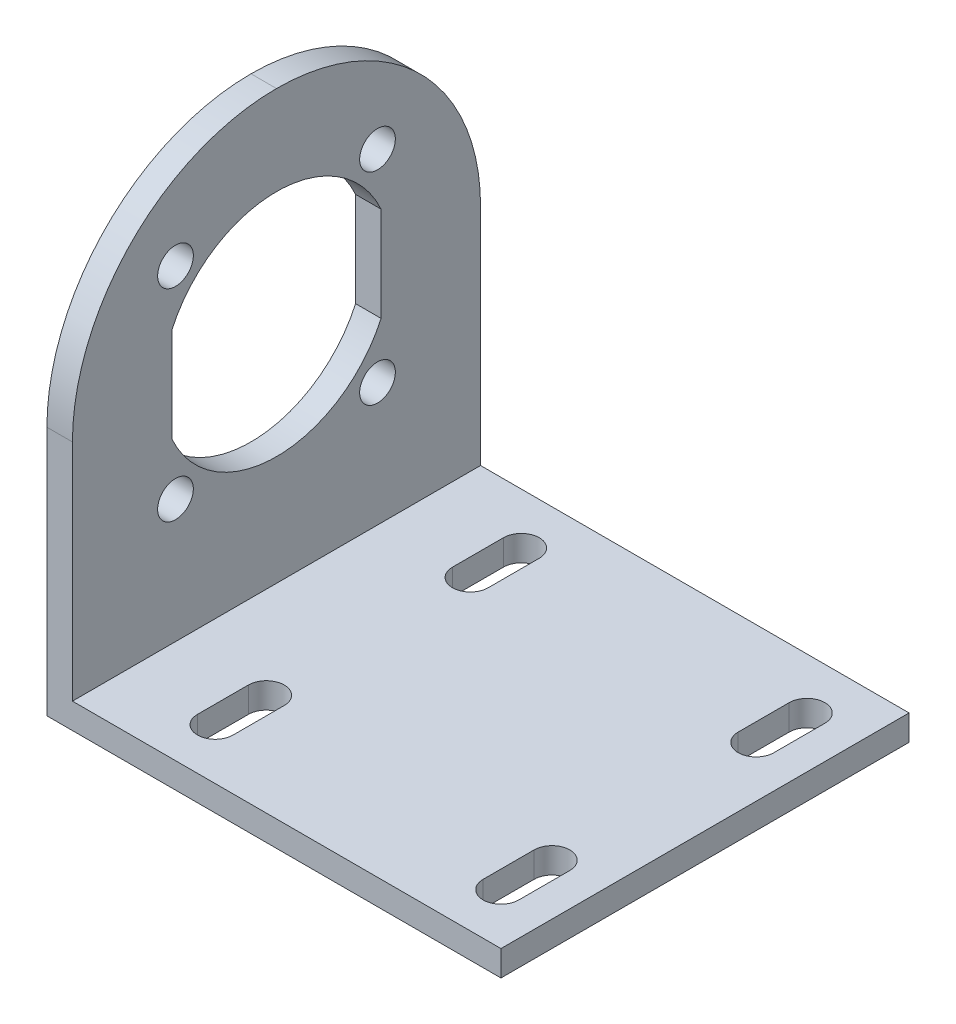
SolidWorks part; units mm, degrees
material "Plain Carbon Steel"
ref_plane "Front Plane"
ref_plane "Top Plane" through (0, 0, 0) normal (0, 1, 0) x (1, 0, 0)
ref_plane "Right Plane" through (0, 0, 0) normal (1, 0, 0) x (0, 0, -1)
sketch "Sketch1" plane through (0, 0, 0) normal (0, 0, 1) x (1, 0, 0)
  line L0 (0, 44.5) -> (0, 0)
  line L1 (0, 0) -> (44.5, 0)
  line L2 (44.5, 0) -> (44.5, 2.5)
  line L3 (44.5, 2.5) -> (2.5, 2.5)
  line L4 (2.5, 2.5) -> (2.5, 44.5)
  line L5 (2.5, 44.5) -> (0, 44.5)
  dimension "D1" = 44.5
  dimension "D2" = 44.5
  dimension "D3" = 2.5
extrude "Boss-Extrude1" add sketch "Sketch1" along normal mid plane 40
fillet "Fillet1" radius 20 2 edges at (1.25, 44.5, -20) (1.25, 44.5, 20)
sketch "Sketch2" plane through (2.5, 0, 0) normal (1, 0, 0) x (0, 0, -1)
  line L0 (10.25, 29.1368) -> (10.25, 19.8632)
  line L1 (-10.25, 29.1368) -> (-10.25, 19.8632)
  line L2 (0, 24.5) -> (9.8995, 14.6005) construction
  line L3 (0, 24.5) -> (4.182, 24.5) construction
  arc A0 (10.25, 29.1368) -> (-10.25, 29.1368) centre (0, 24.5) ccw
  arc A1 (-10.25, 19.8632) -> (10.25, 19.8632) centre (0, 24.5) ccw
  circle A2 centre (0, 24.5) radius 14 construction
  circle A3 centre (9.8995, 14.6005) radius 1.75
  circle A4 centre (-9.8995, 14.6005) radius 1.75
  circle A5 centre (-9.8995, 34.3995) radius 1.75
  circle A6 centre (9.8995, 34.3995) radius 1.75
  point P20 (0, 24.5)
  dimension "D1" = 22.5
  dimension "D4" = 3.5
  dimension "D5" = 28
  dimension "D2" = 10.25
  dimension "D3" = 20.5
  dimension "D6" = 45
  dimension "D8" = 24.5
  dimension "D7" = 4
extrude "Cut-Extrude1" cut sketch "Sketch2" against normal up to next
sketch "Sketch3" plane through (0, 2.5, 0) normal (0, 1, 0) x (1, 0, 0)
  line L0 (11.5, -10) -> (11.5, -15) construction
  line L1 (13.25, -10) -> (13.25, -15)
  line L2 (9.75, -10) -> (9.75, -15)
  line L3 (39.5, -10) -> (39.5, -15) construction
  line L4 (41.25, -10) -> (41.25, -15)
  line L5 (37.75, -10) -> (37.75, -15)
  line L6 (44.5, -20) -> (44.5, 20) construction
  line L8 (11.5, 15) -> (11.5, 10) construction
  line L9 (13.25, 15) -> (13.25, 10)
  line L10 (9.75, 15) -> (9.75, 10)
  line L11 (39.5, 15) -> (39.5, 10) construction
  line L12 (41.25, 15) -> (41.25, 10)
  line L13 (37.75, 15) -> (37.75, 10)
  arc A0 (13.25, -10) -> (9.75, -10) centre (11.5, -10) ccw
  arc A1 (9.75, -15) -> (13.25, -15) centre (11.5, -15) ccw
  arc A2 (41.25, -10) -> (37.75, -10) centre (39.5, -10) ccw
  arc A3 (37.75, -15) -> (41.25, -15) centre (39.5, -15) ccw
  arc A4 (13.25, 15) -> (9.75, 15) centre (11.5, 15) ccw
  arc A5 (9.75, 10) -> (13.25, 10) centre (11.5, 10) ccw
  arc A6 (41.25, 15) -> (37.75, 15) centre (39.5, 15) ccw
  arc A7 (37.75, 10) -> (41.25, 10) centre (39.5, 10) ccw
  point P2 (11.5, -12.5)
  point P9 (39.5, -12.5)
  point P22 (11.5, 12.5)
  point P29 (39.5, 12.5)
  dimension "D2" = 1.75
  dimension "D8" = 1.75
  dimension "D1" = 5
  dimension "D3" = 5
  dimension "D4" = 30
  dimension "D5" = 3.25
  dimension "D6" = 24.5
  dimension "D7" = 5
  dimension "D9" = 5
  dimension "D11" = 12.5
extrude "Cut-Extrude2" cut sketch "Sketch3" against normal up to next
sketch "Sketch5" plane through (2.5, 0, 0) normal (1, 0, 0) x (0, 0, -1)
  line L0 (-10.25, 24.5) -> (-10.25, 2.5) construction
  line L1 (-10.25, 29.1368) -> (-10.25, 19.8632) construction
  line L2 (-20, 2.5) -> (20, 2.5) construction
sketch "Sketch6" plane through (0, 0, 0) normal (-1, 0, 0) x (0, 0, 1)
  line L0 (-10.25, 24.5) -> (-10.25, 0) construction
  line L1 (-10.25, 29.1368) -> (-10.25, 19.8632) construction
  line L2 (20, 0) -> (-20, 0) construction
  line L3 (-10.25, 24.5) -> (10.25, 24.5) construction
  line L4 (10.25, 19.8632) -> (10.25, 29.1368) construction
  line L5 (0, 24.5) -> (0, 0)
